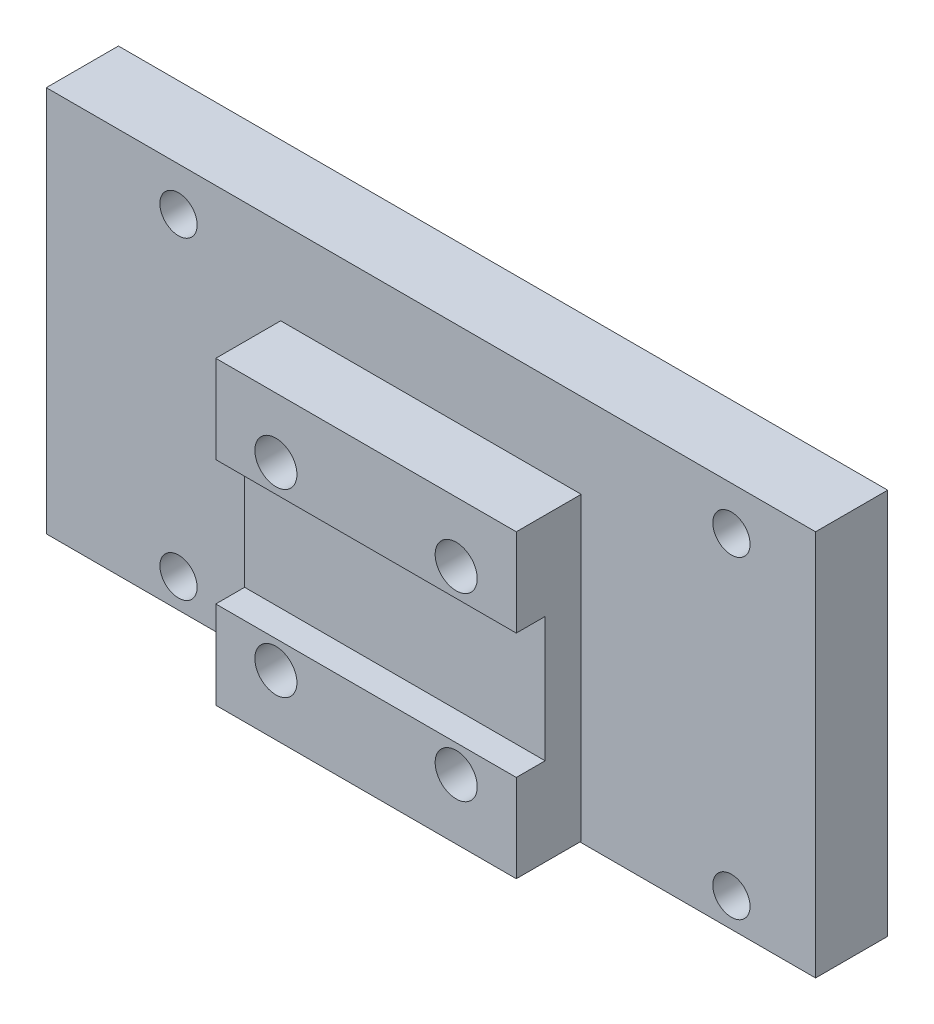
SolidWorks part; units mm, degrees
ref_plane "前视基准面" through (0, 0, 0) normal (0, 0, 1) x (1, 0, 0)
ref_plane "上视基准面" through (0, 0, 0) normal (0, 1, 0) x (1, 0, 0)
ref_plane "右视基准面" through (0, 0, 0) normal (1, 0, 0) x (0, 0, -1)
other "Configuration Table"
sketch "草图1" plane through (0, 0, 0) normal (0, 0, 1) x (1, 0, 0)
  line L5 (0, 0) -> (25, 0)
  line L6 (0, 0) -> (0, 25)
  line L7 (0, 25) -> (25, 25)
  line L8 (25, 0) -> (25, 25)
  line L9 (5, 20) -> (20, 20) construction
  line L10 (5, 20) -> (5, 5) construction
  line L11 (5, 5) -> (20, 5) construction
  line L12 (20, 20) -> (20, 5) construction
  circle A0 centre (5, 20) radius 1.75
  circle A1 centre (20, 20) radius 1.75
  circle A2 centre (5, 5) radius 1.75
  circle A3 centre (20, 5) radius 1.75
  dimension "D4" = 3.5
  dimension "D1" = 25
  dimension "D2" = 25
  dimension "D3" = 15
  dimension "D5" = 5
  dimension "D6" = 5
  dimension "D7" = 15
extrude "凸台-拉伸1" add sketch "草图1" along normal blind 3
sketch "草图2" plane through (0, 0, 3) normal (0, 0, 1) x (1, 0, 0)
  line L0 (0, 17.7) -> (25, 17.7)
  line L1 (0, 25) -> (0, 0) construction
  line L2 (25, 0) -> (25, 25) construction
  line L4 (25, 7.3) -> (0, 7.3)
  line L6 (0, 7.3) -> (0, 0)
  line L7 (25, 17.7) -> (25, 25)
  line L10 (0, 25) -> (0, 0)
  line L11 (0, 0) -> (25, 0)
  line L12 (25, 0) -> (25, 25)
  line L13 (25, 25) -> (0, 25)
  line L14 (0, 25) -> (0, 17.7)
  line L15 (0, 0) -> (25, 0)
  line L16 (25, 0) -> (25, 7.3)
  line L17 (25, 25) -> (0, 25)
  dimension "D1" = 0
  dimension "D2" = 10.4
  dimension "D3" = 7.3
extrude "凸台-拉伸2" add sketch "草图2" along normal blind 2.4
sketch "草图3" plane through (0, 0, 5.4) normal (0, 0, 1) x (1, 0, 0)
  circle A0 centre (5, 5) radius 1.75 construction
  circle A1 centre (20, 5) radius 1.75 construction
  circle A2 centre (20, 20) radius 1.75 construction
  circle A3 centre (5, 20) radius 1.75 construction
  circle A4 centre (5, 5) radius 1.75
  circle A5 centre (20, 5) radius 1.75
  circle A6 centre (20, 20) radius 1.75
  circle A7 centre (5, 20) radius 1.75
extrude "切除-拉伸1" cut sketch "草图3" against normal through all
sketch "草图6" plane through (0, 0, 0) normal (0, 0, -1) x (-1, 0, 0)
  line L0 (0, 25) -> (0, 0) construction
  line L1 (-42.5, 28.05) -> (17.5, 28.05) construction
  line L2 (-42.5, 28.05) -> (-42.5, -3.05) construction
  line L3 (-42.5, -3.05) -> (17.5, -3.05) construction
  line L4 (17.5, 28.05) -> (17.5, -3.05) construction
  line L6 (0, 0) -> (-25, 0) construction
  line L7 (10.5, 2.45) -> (-35.5, 2.45) construction
  line L8 (-35.5, 2.45) -> (-35.5, 22.55) construction
  line L9 (-35.5, 22.55) -> (10.5, 22.55) construction
  line L10 (10.5, 22.55) -> (10.5, 2.45) construction
  line L12 (-44.5, 32.05) -> (19.5, 32.05)
  line L13 (-44.5, 32.05) -> (-44.5, -4.05)
  line L14 (-44.5, -4.05) -> (19.5, -4.05)
  line L15 (19.5, 32.05) -> (19.5, -4.05)
  dimension "D1" = 60
  dimension "D2" = 31.1
  dimension "D3" = 17.5
  dimension "D4" = 3.05
  dimension "D5" = 7
  dimension "D6" = 5.5
  dimension "D8" = 7
  dimension "D9" = 5.5
  dimension "D10" = 2
  dimension "D11" = 4
  dimension "D12" = 2
  dimension "D13" = 1
extrude "凸台-拉伸5" add sketch "草图6" along normal blind 6
sketch "草图7" plane through (0, 0, -6) normal (0, 0, -1) x (-1, 0, 0)
  line L4 (-25, 0) -> (0, 0)
  line L5 (-25, 25) -> (-25, 0)
  line L6 (0, 25) -> (-25, 25)
  line L7 (0, 0) -> (0, 25)
  line L8 (-25, 0) -> (0, 0)
  line L9 (-25, 25) -> (-25, 0)
  line L10 (0, 25) -> (-25, 25)
  line L11 (0, 0) -> (0, 25)
  dimension "D5" = 0
extrude "切除-拉伸2" cut sketch "草图7" against normal blind 5
sketch "草图8" plane through (0, 0, 0) normal (0, 0, 1) x (1, 0, 0)
  circle A1 centre (37.5, 2.3258) radius 1.55
  circle A2 centre (37.5, 2.3258) radius 1.55
  circle A3 centre (-8.5, 2.3258) radius 1.55
  circle A4 centre (-8.5, 2.3258) radius 1.55
  circle A5 centre (-8.5, 28.4258) radius 1.55
  circle A6 centre (-8.5, 28.4258) radius 1.55
  circle A7 centre (37.5, 28.4258) radius 1.55
  circle A8 centre (37.5, 28.4258) radius 1.55
  dimension "D1" = 0
  dimension "D2" = 0
  dimension "D3" = 0
  dimension "D4" = 0
extrude "切除-拉伸3" cut sketch "草图8" against normal blind 36
extrude "切除-拉伸5" cut sketch "草图3<2>" against normal through all
sketch "草图3<2>" plane through (0, 0, 5.4) normal (0, 0, 1) x (1, 0, 0) same geometry as "草图3"
sketch "草图9" plane through (0, 0, 0) normal (0, 0, 1) x (1, 0, 0)
  line L0 (-19.5, -4.05) -> (-19.5, 32.05) construction
  line L1 (-19.5, -0.1) -> (44.5, -0.1)
  line L2 (-19.5, -0.1) -> (-19.5, -4.05)
  line L3 (-19.5, -4.05) -> (44.5, -4.05)
  line L4 (44.5, -0.1) -> (44.5, -4.05)
  dimension "D1" = 3.95
extrude "切除-拉伸6" cut sketch "草图9" against normal through all
